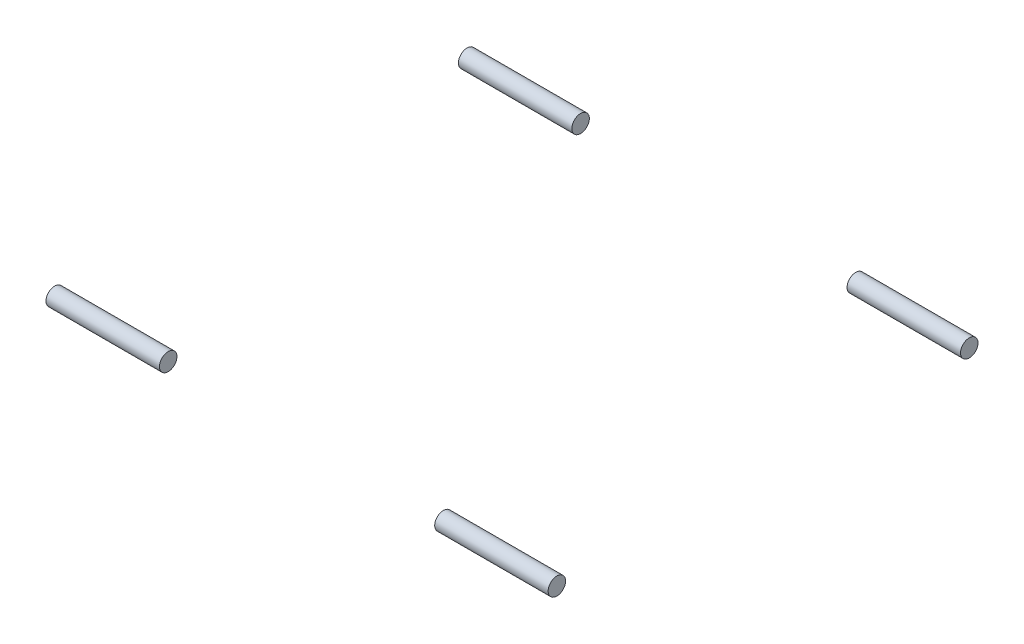
SolidWorks part; units mm, degrees
material "6061-T6 (SS)"
ref_plane "Front Plane" through (0, 0, 0) normal (0, 0, 1) x (1, 0, 0)
ref_plane "Top Plane" through (0, 0, 0) normal (0, 1, 0) x (1, 0, 0)
ref_plane "Right Plane" through (0, 0, 0) normal (1, 0, 0) x (0, 0, -1)
sketch "Sketch1" plane through (91.325, 0, 0) normal (-1, 0, 0) x (0, 0, 1)
  circle A0 centre (150, 0) radius 3.175
  circle A1 centre (0, 0) radius 3.175
  circle A2 centre (0, 0) radius 3.175 construction
  circle A3 centre (150, 0) radius 3.175 construction
extrude "Boss-Extrude1" add sketch "Sketch1" along normal up to surface (41.275 mm away)
mirror "Mirror1" about plane through (0, 0, 0) normal (1, 0, 0) of bodies 101 102
